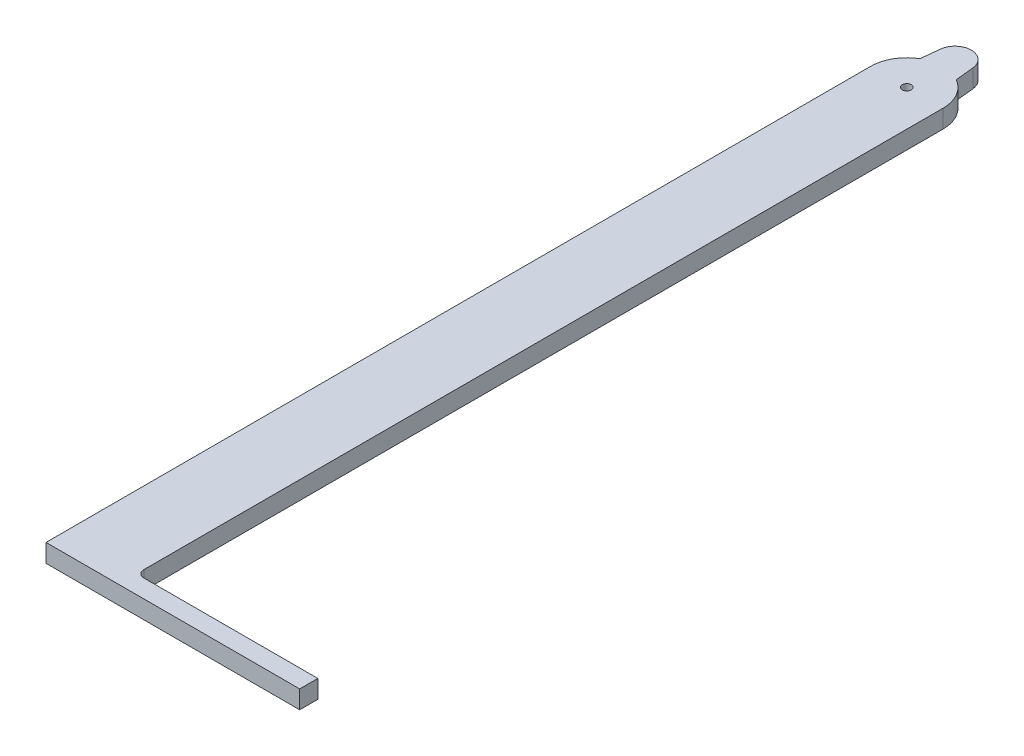
SolidWorks part; units mm, degrees
ref_plane "Front Plane" through (0, 0, 0) normal (0, 0, 1) x (1, 0, 0)
ref_plane "Top Plane" through (0, 0, 0) normal (0, 1, 0) x (1, 0, 0)
ref_plane "Right Plane" through (0, 0, 0) normal (1, 0, 0) x (0, 0, -1)
sketch "Sketch1" plane through (0, 0, 0) normal (0, 1, 0) x (1, 0, 0)
  line L1 (-12.7, 0) -> (12.7, 0)
  line L2 (-12.7, 0) -> (-12.7, -282.575)
  line L3 (-12.7, -282.575) -> (12.7, -282.575)
  line L4 (12.7, 0) -> (12.7, -282.575)
  circle A0 centre (0, 0) radius 12.7
  dimension "D1" = 25.4
  dimension "D2" = 282.575
extrude "Boss-Extrude1" add sketch "Sketch1" along normal blind 6.35 contours A0 L2 L3 L4 | L1 A0 | L1 A0 region at (0, 0, -5.39) region at (0, 0, 146.26) region at (0, 0, 5.39)
sketch "Sketch2" plane through (0, 6.35, 0) normal (0, 1, 0) x (1, 0, 0)
  line L1 (-12.7, -282.575) -> (76.2, -282.575)
  line L2 (-12.7, -282.575) -> (-12.7, -288.925)
  line L3 (-12.7, -288.925) -> (76.2, -288.925)
  line L4 (76.2, -282.575) -> (76.2, -288.925)
  dimension "D1" = 88.9
  dimension "D2" = 6.35
extrude "Boss-Extrude2" add sketch "Sketch2" against normal up to surface (6.35 mm away) up to face at (0, 0, 138.1125)
fillet "Fillet1" radius 2.54 1 edges
sketch "Sketch3" plane through (0, 0, 0) normal (0, -1, 0) x (-1, 0, 0)
  line L4 (-7.3841, 1.2138) -> (7.3841, 1.2138)
  line L6 (-7.3841, 1.2138) -> (-5.6981, 17.4684)
  line L7 (5.6981, 17.4684) -> (7.3841, 1.2138)
  line L8 (-7.3841, 1.2138) -> (-5.6981, 17.4684)
  line L9 (5.6981, 17.4684) -> (7.3841, 1.2138)
  arc A3 (5.6981, 17.4684) -> (-5.6981, 17.4684) centre (0, 16.8774) ccw
  arc A4 (5.6981, 17.4684) -> (-5.6981, 17.4684) centre (0, 16.8774) ccw
  dimension "D1" = 3.175
extrude "Boss-Extrude3" add sketch "Sketch3" against normal up to surface (6.35 mm away) up to face at (28.2277, 6.35, 181.5491)
sketch "Sketch4" plane through (0, 0, 0) normal (0, -1, 0) x (-1, 0, 0)
  circle A0 centre (0, 0) radius 1.5875
  dimension "D1" = 3.175
extrude "Cut-Extrude1" cut sketch "Sketch4" against normal through all
